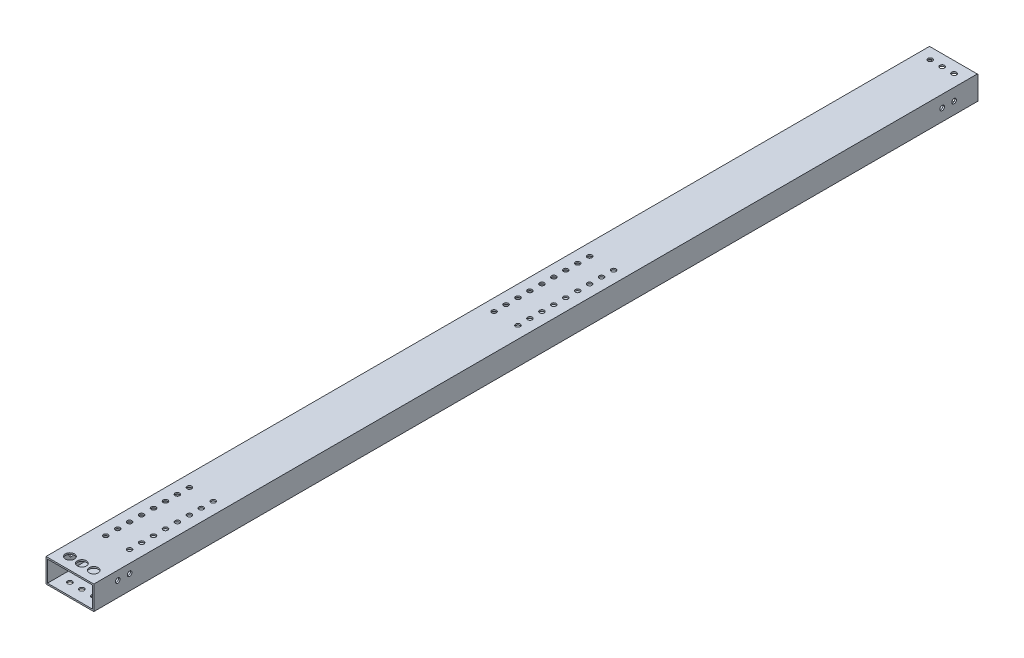
SolidWorks part; units mm, degrees
material "6061-T6 (SS)"
ref_plane "Front Plane" through (0, 0, 0) normal (0, 0, 1) x (1, 0, 0)
ref_plane "Top Plane" through (0, 0, 0) normal (0, 1, 0) x (1, 0, 0)
ref_plane "Right Plane" through (0, 0, 0) normal (1, 0, 0) x (0, 0, -1)
sketch "Sketch1" plane through (0, 0, 0) normal (0, 0, 1) x (1, 0, 0)
  line L0 (-23.8125, 11.1125) -> (23.8125, 11.1125)
  line L1 (-25.4, -12.7) -> (25.4, -12.7)
  line L2 (-25.4, -12.7) -> (-25.4, 12.7)
  line L3 (-25.4, 12.7) -> (25.4, 12.7)
  line L4 (25.4, -12.7) -> (25.4, 12.7)
  line L5 (-25.4, -12.7) -> (25.4, 12.7) construction
  line L6 (-25.4, 12.7) -> (25.4, -12.7) construction
  line L7 (23.8125, -11.1125) -> (23.8125, 11.1125)
  line L8 (-23.8125, -11.1125) -> (23.8125, -11.1125)
  line L9 (-23.8125, -11.1125) -> (-23.8125, 11.1125)
  point P0 (0, 0)
  dimension "D1" = 50.8
  dimension "D2" = 25.4
  dimension "D3" = 1.5875
extrude "Boss-Extrude1" add sketch "Sketch1" along normal mid plane 939.8
sketch "Sketch4" plane through (0, 12.7, 0) normal (0, 1, 0) x (1, 0, 0)
  line L0 (25.4, -469.9) -> (-25.4, -469.9) construction
  circle A0 centre (-12.7, -457.2) radius 4.826
  circle A1 centre (0, -457.2) radius 4.826
  circle A2 centre (12.7, -457.2) radius 4.826
  dimension "D1" = 9.652
  dimension "D2" = 12.7
  dimension "D3" = 12.7
  dimension "D4" = 12.7
extrude "Cut-Extrude3" cut sketch "Sketch4" against normal up to surface (1.5875 mm away) contours A0 | A1 | A2 region at (-12.7, 12.7, 457.2) region at (0, 12.7, 457.2) region at (12.7, 12.7, 457.2) up to face at (0, 11.1125, 0)
sketch "Sketch5" plane through (0, -12.7, 0) normal (0, -1, 0) x (1, 0, 0)
  circle A0 centre (-12.7, 457.2) radius 4.826 construction
  circle A1 centre (0, 457.2) radius 4.826 construction
  circle A2 centre (12.7, 457.2) radius 4.826 construction
  circle A3 centre (-12.7, 457.2) radius 4.826
  circle A4 centre (0, 457.2) radius 4.826
  circle A5 centre (12.7, 457.2) radius 4.826
  circle A6 centre (-12.7, 457.2) radius 2.5527
  circle A7 centre (0, 457.2) radius 2.5527
  circle A8 centre (12.7, 457.2) radius 2.5527
  dimension "D1" = 5.1054
extrude "Cut-Extrude4" cut sketch "Sketch5" against normal up to surface (1.5875 mm away) contours A8 | A7 | A6 region at (-12.7, -12.7, 457.2) region at (0, -12.7, 457.2) region at (12.7, -12.7, 457.2) up to face at (0, -11.1125, 0)
sketch "Sketch6" plane through (0, -12.7, 0) normal (0, -1, 0) x (1, 0, 0)
  line L0 (-25.4, -469.9) -> (25.4, -469.9) construction
  circle A0 centre (-12.7, -457.2) radius 2.5527
  circle A1 centre (0, -457.2) radius 2.5527
  circle A2 centre (12.7, -457.2) radius 2.5527
  dimension "D1" = 5.1054
  dimension "D2" = 12.7
  dimension "D3" = 12.7
  dimension "D4" = 12.7
extrude "Cut-Extrude5" cut sketch "Sketch6" against normal through all contours A2 | A1 | A0 region at (-12.7, -12.7, -457.2) region at (0, -12.7, -457.2) region at (12.7, -12.7, -457.2)
sketch "Sketch7" plane through (25.4, 0, 0) normal (1, 0, 0) x (0, 0, -1)
  line L0 (-469.9, -12.7) -> (-469.9, 12.7) construction
  line L2 (469.9, -12.7) -> (469.9, 12.7) construction
  line L3 (-469.9, -12.7) -> (469.9, -12.7) construction
  circle A0 centre (-457.2, 3.175) radius 2.4892
  circle A1 centre (-444.5, 3.175) radius 2.4892
  circle A2 centre (-431.8, 3.175) radius 2.4892
  circle A3 centre (-419.1, 3.175) radius 2.4892
  circle A4 centre (457.2, 0) radius 2.4892
  circle A5 centre (444.5, 0) radius 2.4892
  circle A6 centre (431.8, 0) radius 2.4892
  dimension "D1" = 4.9784
  dimension "D7" = 4.9784
  dimension "D8" = 12.7
  dimension "D2" = 12.7
  dimension "D3" = 12.7
  dimension "D4" = 12.7
  dimension "D5" = 12.7
  dimension "D6" = 15.875
  dimension "D9" = 12.7
  dimension "D10" = 12.7
  dimension "D11" = 12.7
extrude "Cut-Extrude6" cut sketch "Sketch7" against normal through all contours A6 | A5 | A1 | A2 region at (25.4, 3.175, 444.5) region at (25.4, 3.175, 431.8) region at (25.4, 0, -444.5) region at (25.4, 0, -431.8)
sketch "Sketch10" plane through (0, 12.7, 0) normal (0, 1, 0) x (1, 0, 0)
  line L1 (25.4, -469.9) -> (-25.4, -469.9) construction
  line L3 (-25.4, -469.9) -> (-25.4, 469.9) construction
  circle A0 centre (-12.7, -419.1) radius 2.4892
  circle A5 centre (12.7, -419.1) radius 2.4892
  circle A6 centre (-12.7, -406.4) radius 2.4892
  circle A7 centre (12.7, -406.4) radius 2.4892
  circle A8 centre (-12.7, -393.7) radius 2.4892
  circle A9 centre (12.7, -393.7) radius 2.4892
  circle A10 centre (-12.7, -381) radius 2.4892
  circle A11 centre (12.7, -381) radius 2.4892
  circle A12 centre (-12.7, -368.3) radius 2.4892
  circle A13 centre (12.7, -368.3) radius 2.4892
  circle A14 centre (-12.7, -355.6) radius 2.4892
  circle A15 centre (12.7, -355.6) radius 2.4892
  circle A16 centre (-12.7, -342.9) radius 2.4892
  circle A17 centre (12.7, -342.9) radius 2.4892
  circle A18 centre (-12.7, -330.2) radius 2.4892
  circle A19 centre (12.7, -330.2) radius 2.4892
  circle A20 centre (-12.7, -6.35) radius 2.4892
  circle A21 centre (12.7, -6.35) radius 2.4892
  circle A22 centre (-12.7, 6.35) radius 2.4892
  circle A23 centre (12.7, 6.35) radius 2.4892
  circle A24 centre (-12.7, 19.05) radius 2.4892
  circle A25 centre (12.7, 19.05) radius 2.4892
  circle A26 centre (-12.7, 31.75) radius 2.4892
  circle A27 centre (12.7, 31.75) radius 2.4892
  circle A28 centre (-12.7, 44.45) radius 2.4892
  circle A29 centre (12.7, 44.45) radius 2.4892
  circle A30 centre (-12.7, 57.15) radius 2.4892
  circle A31 centre (12.7, 57.15) radius 2.4892
  circle A32 centre (-12.7, 69.85) radius 2.4892
  circle A33 centre (12.7, 69.85) radius 2.4892
  circle A34 centre (-12.7, 82.55) radius 2.4892
  circle A35 centre (12.7, 82.55) radius 2.4892
  circle A36 centre (-12.7, 95.25) radius 2.4892
  circle A37 centre (12.7, 95.25) radius 2.4892
  dimension "D1" = 25.4
  dimension "D3" = 4.9784
  dimension "D2" = 12.7
  dimension "D4" = 50.8
  dimension "D5" = 12.7
  dimension "D6" = 323.85
  dimension "D8" = 12.7
  dimension "D9" = 9
extrude "Cut-Extrude8" cut sketch "Sketch10" against normal up to next (1.5875 mm away)
chamfer "Chamfer1" distance 0.762 angle 45 1 edges at (0, 12.7, -469.9)
